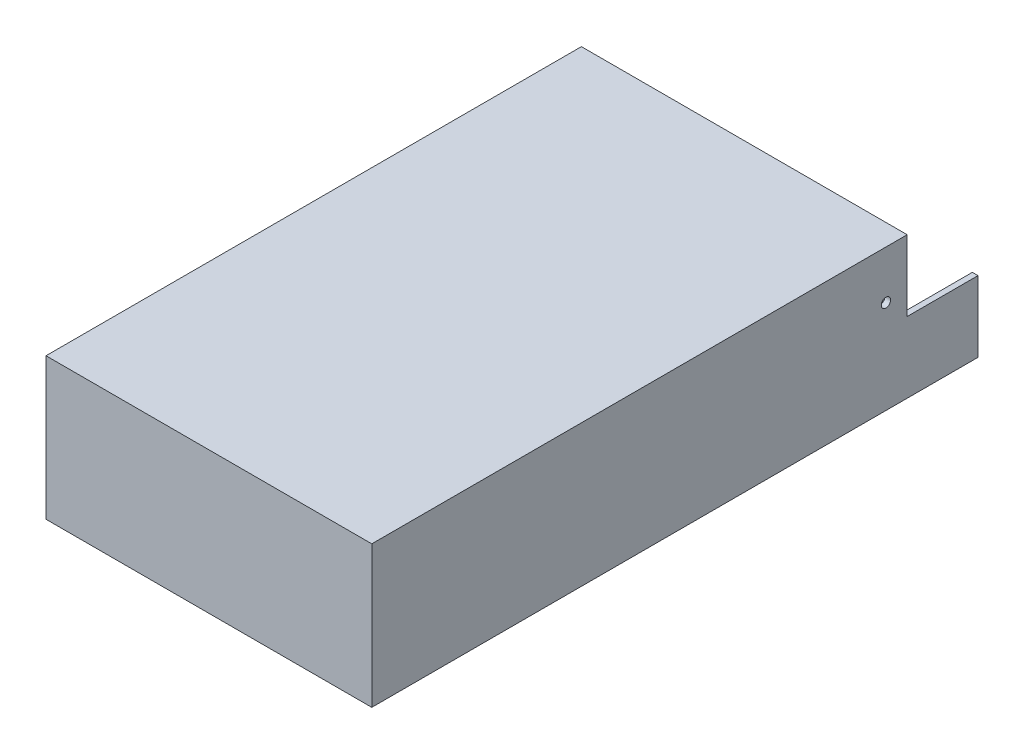
SolidWorks part; units mm, degrees
ref_plane "Front" through (0, 0, 0) normal (0, 0, 1) x (1, 0, 0)
ref_plane "Top" through (0, 0, 0) normal (0, 1, 0) x (1, 0, 0)
ref_plane "Right" through (0, 0, 0) normal (1, 0, 0) x (0, 0, -1)
sketch "Sketch1" plane through (0, 0, 0) normal (0, 1, 0) x (1, 0, 0)
  line L1 (0, 0) -> (115, 0)
  line L2 (0, 0) -> (0, 214)
  line L3 (0, 214) -> (115, 214)
  line L4 (115, 0) -> (115, 214)
  dimension "D1" = 115
  dimension "D2" = 214
extrude "Boss-Extrude1" add sketch "Sketch1" along normal blind 50
sketch "Sketch4" plane through (115, 0, 0) normal (1, 0, 0) x (0, 0, -1)
  line L0 (0, 0) -> (214, 0) construction
  line L1 (214, 50) -> (189, 50)
  line L2 (214, 50) -> (214, 25)
  line L3 (214, 25) -> (189, 25)
  line L4 (189, 50) -> (189, 25)
  dimension "D1" = 25
  dimension "D2" = 25
extrude "Cut-Extrude1" cut sketch "Sketch4" against normal through all
shell "Shell1" thickness 2 removed face at (57.5, 12.5, -214) removed face at (57.5, 25, -201.5)
hole_wizard "M4 Clearance Hole1" positions "Sketch2" profile "Sketch3" hole size "M4" standard "ANSI Metric"
sketch "Sketch2" plane through (0, 0, 0) normal (0, -1, 0) x (-1, 0, 0)
  line L9 (-57.5, 214) -> (-57.5, 0) construction
  line L10 (-115, 214) -> (0, 214) construction
  line L11 (0, 0) -> (-115, 0) construction
  line L15 (-82.5, 32) -> (-32.5, 32)
  line L16 (-82.5, 32) -> (-82.5, 182)
  line L17 (-82.5, 182) -> (-32.5, 182)
  line L18 (-32.5, 32) -> (-32.5, 182)
  line L19 (-82.5, 32) -> (-32.5, 182) construction
  line L20 (-82.5, 182) -> (-32.5, 32) construction
  point P80 (-57.5, 107)
  point P81 (-32.5, 182)
  point P84 (-82.5, 32)
  point P85 (-82.5, 182)
  point P86 (-32.5, 32)
  dimension "D1" = 50
  dimension "D2" = 150
sketch "Sketch3" plane through (32.5, 0, -32) normal (1, 0, 0) x (0, 0, -1)
  line L0 (0, 0) -> (0, 5.2919)
  line L1 (0, 5.2919) -> (2.15, 4)
  line L2 (2.15, 4) -> (2.15, 0)
  line L5 (2.15, 0) -> (0, 0)
  line L10 (0, 5.2919) -> (-2.15, 4) construction
  line L11 (0, -6.35) -> (0, 107.95) construction
  dimension "Hole Dia." = 4.3
  dimension "Hole Depth" = 4
  dimension "Drill Angle" = 118
sketch "Sketch7" plane through (115, 0, 0) normal (1, 0, 0) x (0, 0, -1)
  line L0 (214, 25) -> (214, 0) construction
  line L1 (0, 50) -> (189, 50) construction
  point P0 (181.5, 33)
  dimension "D1" = 32.5
  dimension "D2" = 17
hole_wizard "Tap Drill for M4 Tap1" positions "Sketch7" profile "Sketch6" hole size "M4" standard "ISO" end condition through all
sketch "Sketch6" plane through (115, 33, -181.5) normal (0, 1, 0) x (0, 0, -1)
  line L0 (0, 0) -> (0, 115)
  line L1 (0, 115) -> (1.65, 115)
  line L2 (1.65, 115) -> (1.65, 0)
  line L5 (1.65, 0) -> (0, 0)
  line L11 (0, -6.35) -> (0, 107.95) construction
  dimension "Thru Hole Dia." = 3.3
  dimension "Thru Hole Depth" = 115
